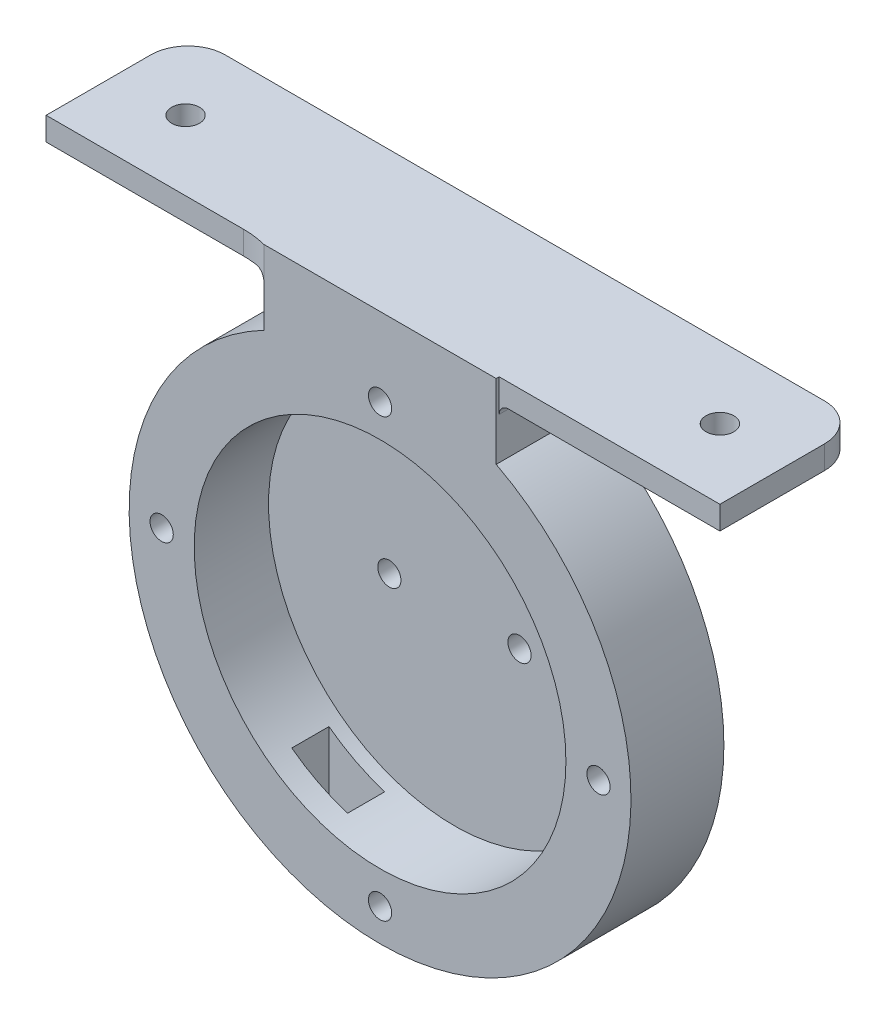
SolidWorks part; units mm, degrees
ref_plane "Front Plane" through (0, 0, 0) normal (0, 0, 1) x (1, 0, 0)
ref_plane "Top Plane" through (0, 0, 0) normal (0, 1, 0) x (1, 0, 0)
ref_plane "Right Plane" through (0, 0, 0) normal (1, 0, 0) x (0, 0, -1)
sketch "Sketch1" plane through (0, 0, 0) normal (0, 0, 1) x (1, 0, 0)
  circle A0 centre (0, 0) radius 27
  circle A1 centre (0, 0) radius 23.5 construction
  circle A2 centre (0, 23.5) radius 1.25
  circle A3 centre (23.5, 0) radius 1.25
  circle A4 centre (0, -23.5) radius 1.25
  circle A5 centre (-23.5, 0) radius 1.25
  circle A6 centre (0, 0) radius 20
  point P15 (0, 0)
  dimension "D1" = 54
  dimension "D2" = 47
  dimension "D3" = 2.5
  dimension "D5" = 40
  dimension "D4" = 4
extrude "Boss-Extrude1" add sketch "Sketch1" along normal blind 10
sketch "Sketch3" plane through (0, 0, 0) normal (0, 0, 1) x (1, 0, 0)
  circle A0 centre (0, 0) radius 20
  circle A1 centre (0, 0) radius 7 construction
  circle A2 centre (-7, 0) radius 1.25
  circle A3 centre (7, 0) radius 1.25
  circle A4 centre (0, 0) radius 11.5 construction
  dimension "D1" = 40
  dimension "D2" = 14
  dimension "D3" = 2.5
  dimension "D4" = 23
extrude "Boss-Extrude2" add sketch "Sketch3" along normal blind 2
sketch "Sketch5" plane through (0, 0, 10) normal (0, 0, 1) x (1, 0, 0)
  line L0 (0, -5.5) -> (0, 5.5) construction
  line L1 (-12.5, 23.9322) -> (-4.2519, 23.9322)
  line L2 (-12.5, 23.9322) -> (-12.5, 31.9322)
  line L3 (-12.5, 31.9322) -> (12.5, 31.9322)
  line L4 (12.5, 23.9322) -> (12.5, 31.9322)
  line L5 (4.2678, 23.9322) -> (0, 26.2545)
  line L6 (0, 26.2545) -> (-4.2519, 23.9322)
  line L7 (4.2678, 23.9322) -> (12.5, 23.9322)
  circle A0 centre (0, 0) radius 27 construction
  dimension "D1" = 12.5
  dimension "D2" = 25
  dimension "D3" = 8
extrude "Boss-Extrude3" add sketch "Sketch5" against normal blind 6
sketch "Sketch4" plane through (0, 0, 0) normal (0, 1, 0) x (1, 0, 0)
  line L0 (27, -10) -> (-27, -10) construction
  line L1 (-12, -3.5) -> (-6, -3.5)
  line L2 (-12, -3.5) -> (-12, -7.5)
  line L3 (-12, -7.5) -> (-6, -7.5)
  line L4 (-6, -3.5) -> (-6, -7.5)
  dimension "D1" = 4
  dimension "D2" = 6
  dimension "D3" = 2.5
  dimension "D4" = 6
extrude "Cut-Extrude1" cut sketch "Sketch4" against normal up to surface (26.3249 mm away) up to face at (0, 11.9661, 7)
sketch "Sketch6" plane through (0, 31.9322, 0) normal (0, 1, 0) x (1, 0, 0)
  line L0 (12.5, -4) -> (12.5, -10) construction
  line L1 (-12.5, -10) -> (12.5, -10)
  line L2 (-12.5, -10) -> (-12.5, 5.32)
  line L3 (-12.5, 5.32) -> (12.5, 5.32)
  line L4 (12.5, -10) -> (12.5, 5.32)
  dimension "D1" = 15.32
extrude "Boss-Extrude4" add sketch "Sketch6" against normal blind 2.5
sketch "Sketch7" plane through (0, 31.9322, 0) normal (0, 1, 0) x (1, 0, 0)
  line L0 (0, -8.426) -> (0, 8.426) construction
  line L1 (-36.25, -66.92) -> (36.25, -66.92) construction
  line L2 (-36.25, -66.92) -> (-36.25, 1.58) construction
  line L3 (-32.25, 5.58) -> (32.25, 5.58) construction
  line L4 (36.25, -66.92) -> (36.25, 1.58) construction
  line L5 (-28.75, -9.68) -> (-36.25, -9.68)
  line L6 (0, 5.58) -> (-32.25, 5.58)
  line L7 (-36.25, -9.68) -> (-36.25, -1.92)
  line L8 (12.5, -4) -> (-12.5, -4) construction
  line L9 (0, 5.58) -> (0, -9.68)
  line L10 (0, -9.68) -> (-28.75, -9.68)
  line L11 (-36.25, 1.58) -> (-36.25, -1.92)
  arc A0 (32.25, 5.58) -> (36.25, 1.58) centre (32.25, 1.58) cw construction
  arc A1 (-36.25, 1.58) -> (-32.25, 5.58) centre (-32.25, 1.58) cw
  circle A3 centre (-28.75, -2.18) radius 1.5
  point P4 (0, 5.58)
  point P11 (36.25, 5.58)
  point P14 (-36.25, 5.58)
  point P21 (-36.25, -9.68)
  point P23 (0, 0)
  point P24 (0, 0)
  point P25 (0, 0)
  point P26 (-32.25, 5.32)
  point P27 (0, 0)
  point P28 (0, 0)
  point P30 (-32.25, 5.32)
  point P31 (0, 0)
  point P32 (-36.25, 1.32)
  point P33 (-32.25, 5.32)
  dimension "D4" = 4
  dimension "D7" = 3
  dimension "D1" = 72.5
  dimension "D2" = 72.5
  dimension "D3" = 9.58
extrude "Boss-Extrude5" add sketch "Sketch7" against normal blind 2.5 contours L10 L9 L6 A1 L11 A3 region at (-17.8776, 31.9322, 2.0909)
fillet "Fillet2" radius 10 1 edges at (-12.5, 30.6822, 9.68)
sketch "Sketch8" plane through (0, 31.9322, 0) normal (0, 1, 0) x (1, 0, 0)
  circle A0 centre (-28.75, -2.18) radius 2.5
  circle A1 centre (-28.75, -2.18) radius 4
  dimension "D1" = 5
  dimension "D2" = 8
extrude "Boss-Extrude6" [suppressed] add sketch "Sketch8" against normal blind 5
mirror "Mirror1" about plane through (0, 0, 0) normal (1, 0, 0) of "Boss-Extrude4", "Boss-Extrude5", "Boss-Extrude6"
fillet "Fillet3" radius 1 3 edges at (0, 29.4322, 4) (12.5, 29.4322, 6.84) (-12.5, 29.4322, 7)
fillet "Fillet4" [suppressed] radius 10
